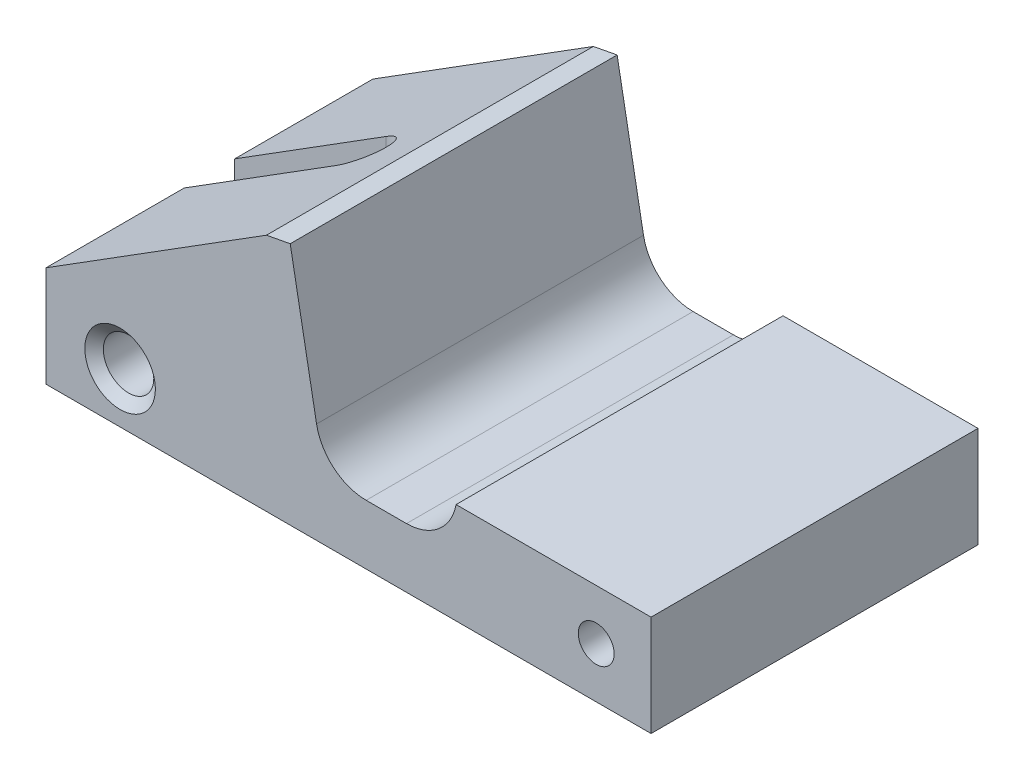
SolidWorks part; units mm, degrees
material "6061-T6 (SS)"
ref_plane "Front Plane" through (0, 0, 0) normal (0, 0, 1) x (1, 0, 0)
ref_plane "Top Plane" through (0, 0, 0) normal (0, 1, 0) x (1, 0, 0)
ref_plane "Right Plane" through (0, 0, 0) normal (1, 0, 0) x (0, 0, -1)
sketch "Sketch1" plane through (0, 0, 0) normal (0, 0, 1) x (1, 0, 0)
  line L0 (-76.567, -68.5403) -> (-62.6865, -59.8235)
  line L1 (-76.567, -68.5403) -> (-38.467, -68.5403)
  line L2 (-76.567, -68.5403) -> (-76.567, -74.8903)
  line L3 (-76.567, -74.8903) -> (-38.467, -74.8903)
  line L4 (-38.467, -68.5403) -> (-38.467, -74.8903)
  line L5 (-62.6865, -59.8235) -> (-61.1892, -59.5393)
  line L6 (-61.1892, -59.5393) -> (-59.5301, -68.5403)
  dimension "D1" = 6.35
  dimension "D2" = 38.1
extrude "Boss-Extrude1" add sketch "Sketch1" along normal offset from surface (20.5861 mm away) 1.27 from offset 1.27 contours L4 L1 L2 L3 | L6 L5 L0 L1 | L2 region at (-65.8211, -65.3771, 0) region at (-57.517, -71.7153, 0)
sketch "Sketch2" plane through (26.5539, -74.8903, 0) normal (0, 1, 0) x (1, 0, 0)
  line L0 (-103.1209, -11.5631) -> (-93.5959, -11.5631) construction
  line L1 (-103.1209, -21.8561) -> (-103.1209, -1.27) construction
  line L2 (-103.1209, -13.1506) -> (-93.5959, -13.1506)
  line L3 (-103.1209, -9.9756) -> (-93.5959, -9.9756)
  arc A0 (-103.1209, -13.1506) -> (-103.1209, -9.9756) centre (-103.1209, -11.5631) cw
  arc A1 (-93.5959, -13.1506) -> (-93.5959, -9.9756) centre (-93.5959, -11.5631) ccw
  dimension "D1" = 1.5875
  dimension "D3" = 9.525
  dimension "D2" = 1.5875
extrude "Cut-Extrude1" cut sketch "Sketch2" along normal through all
hole_wizard "1/8 (0.125) Diameter Hole1" positions "Sketch4" profile "Sketch3" hole size "1/8" standard "ANSI Inch" end condition through all
sketch "Sketch4" plane through (0, 0, 21.8561) normal (0, 0, 1) x (1, 0, 0)
  line L0 (-71.9014, -71.7153) -> (-71.9014, -92.3503) construction
  line L2 (-75.8114, -97.0903) -> (-75.8114, -139.1903) construction
  line L3 (-76.567, -71.7153) -> (-38.467, -71.7153) construction
  line L4 (-76.567, -74.8903) -> (-76.567, -68.5403) construction
  line L5 (-38.467, -74.8903) -> (-38.467, -68.5403) construction
  point P0 (-71.9014, -71.7153)
sketch "Sketch3" plane through (-71.9014, -71.7153, 21.8561) normal (1, 0, 0) x (0, -1, 0)
  line L0 (0, 0) -> (0, 20.5861)
  line L1 (0, 20.5861) -> (1.5875, 20.5861)
  line L2 (1.5875, 20.5861) -> (1.5875, 0.5328)
  line L3 (1.5875, 0.5328) -> (2.2225, 0)
  line L5 (2.2225, 0) -> (0, 0)
  line L6 (-1.5875, 0.5328) -> (-2.2225, 0) construction
  line L11 (0, -6.35) -> (0, 107.95) construction
  dimension "Thru Hole Dia." = 3.175
  dimension "Thru Hole Depth" = 20.5861
  dimension "Near C'Sink Dia." = 4.445
  dimension "Near C'Sink Angle" = 100
hole_wizard "#4-40 Tapped Hole1" positions "Sketch6" profile "Sketch5" tap size "#4-40" standard "ANSI Inch" end condition through all
sketch "Sketch6" plane through (0, 0, 21.8561) normal (0, 0, 1) x (1, 0, 0)
  line L0 (-38.467, -74.8903) -> (-38.467, -68.5403) construction
  point P0 (-41.9214, -71.7153)
  point P7 (-38.467, -71.7153)
  dimension "D1" = 3.4544
sketch "Sketch5" plane through (-41.9214, -71.7153, 21.8561) normal (1, 0, 0) x (0, -1, 0)
  line L0 (0, 0) -> (0, 20.5861)
  line L1 (0, 20.5861) -> (1.1303, 20.5861)
  line L2 (1.1303, 20.5861) -> (1.1303, 0)
  line L5 (1.1303, 0) -> (0, 0)
  line L11 (0, -6.35) -> (0, 107.95) construction
  dimension "Thru Tap Drill Dia." = 2.2606
  dimension "Thru Tap Drill Depth" = 20.5861
cosmetic thread "Hole Thread1" parameters "D2"=2.8448
sketch "Sketch7" plane through (0, 0, 21.8561) normal (0, 0, 1) x (1, 0, 0)
  line L3 (-53.8677, -67.9648) -> (-56.4077, -67.9648) construction
  line L5 (-53.8677, -71.1398) -> (-56.4077, -71.1398)
  line L6 (-53.8677, -64.7898) -> (-56.4077, -64.7898)
  line L7 (-59.5301, -68.5403) -> (-61.1892, -59.5393) construction
  arc A0 (-53.8677, -71.1398) -> (-53.8677, -64.7898) centre (-53.8677, -67.9648) ccw
  arc A1 (-56.4077, -64.7898) -> (-56.4077, -71.1398) centre (-56.4077, -67.9648) ccw
  point P2 (-59.5301, -68.5403)
  point P3 (-59.5827, -67.9648)
  point P4 (-55.1377, -67.9648)
  point P17 (-50.6927, -67.9648)
  dimension "D1" = 3.175
  dimension "D2" = 8.89
extrude "Cut-Extrude2" cut sketch "Sketch7" against normal through all
